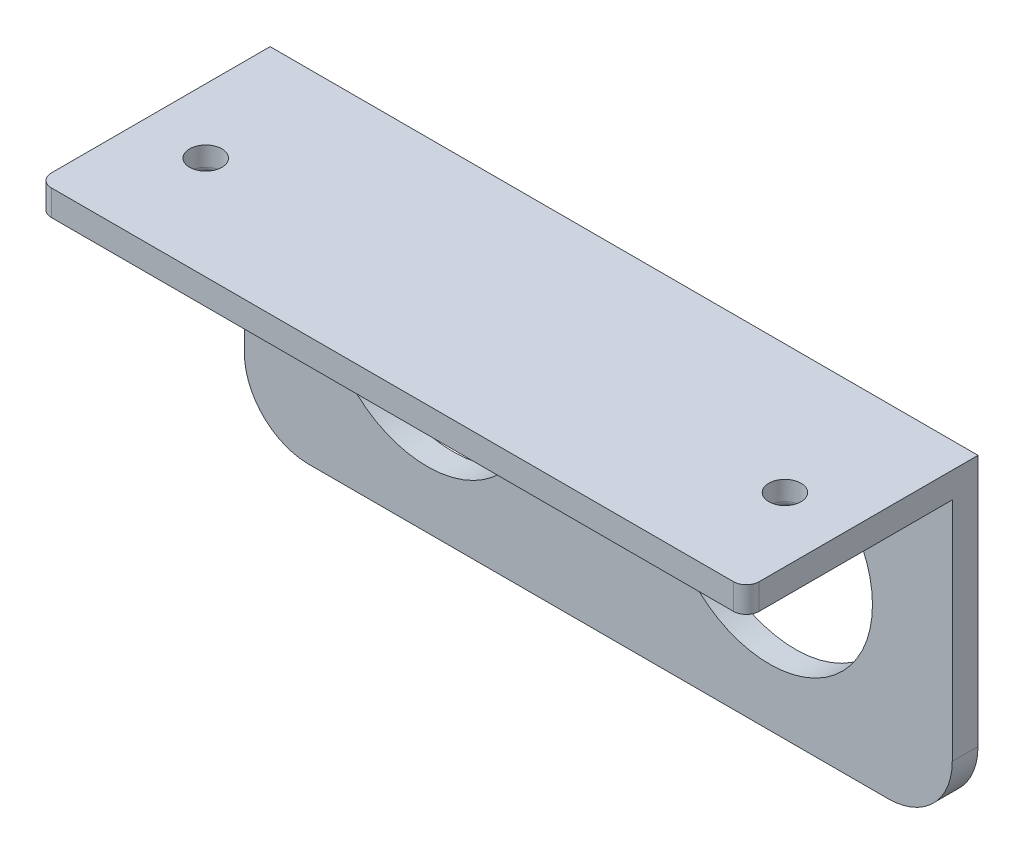
SolidWorks part; units mm, degrees
other "Markup1"
sketch "Sketch7" plane through (-20.0719, -0.3318, 12) normal (-0.8831, -0.2604, 0.3903) x (-0.3657, -0.1393, -0.9203)
other "Markup2"
sketch "Sketch23" plane through (-28.5719, 1.0682, 18) normal (-0.0368, -0.1105, 0.9932) x (-0.9991, 0.0251, -0.0342)
other "Markup3"
sketch "Sketch24" plane through (-28.5719, 1.0682, 18) normal (-0.0368, -0.1105, 0.9932) x (-0.9991, 0.0251, -0.0342)
ref_plane "Front Plane" through (0, 0, 0) normal (0, 0, 1) x (1, 0, 0)
ref_plane "Top Plane" through (0, 0, 0) normal (0, 1, 0) x (1, 0, 0)
ref_plane "Right Plane" through (0, 0, 0) normal (1, 0, 0) x (0, 0, -1)
sketch "Sketch1" plane through (0, 0, 0) normal (0, 0, 1) x (1, 0, 0)
  line L1 (-28.5719, 23.6682) -> (26.4281, 23.6682)
  line L2 (-28.5719, 23.6682) -> (-28.5719, 1.0682)
  line L3 (-28.5719, 1.0682) -> (26.4281, 1.0682)
  line L4 (26.4281, 23.6682) -> (26.4281, 1.0682)
  dimension "D1" = 55
  dimension "D2" = 22.6
extrude "Boss-Extrude1" add sketch "Sketch1" along normal blind 2 contours L1 L4 L3 L2
sketch "Sketch2" plane through (0, 0, 2) normal (0, 0, 1) x (1, 0, 0)
  line L1 (-28.5719, 23.6682) -> (26.4281, 23.6682) construction
  line L4 (-28.5719, 23.6682) -> (-28.5719, 1.0682) construction
  circle A0 centre (-14.3719, 13.5182) radius 8
  circle A1 centre (12.2281, 13.5182) radius 8
  dimension "D5" = 16
  dimension "D6" = 16
  dimension "D1" = 26.6
  dimension "D2" = 10.15
  dimension "D3" = 14.2
  dimension "D4" = 10.15
extrude "Cut-Extrude2" cut sketch "Sketch2" against normal blind 2 contours A0
extrude "Cut-Extrude3" cut sketch "Sketch2<4>" against normal blind 2
sketch "Sketch2<4>" plane through (0, 0, 2) normal (0, 0, 1) x (1, 0, 0) same geometry as "Sketch2"
sketch "Sketch5" plane through (0, 0, 2) normal (0, 0, 1) x (1, 0, 0)
  line L0 (-28.5719, 23.6682) -> (26.4281, 23.6682) construction
  line L1 (-6.5719, 23.6682) -> (4.4281, 23.6682)
  line L2 (-6.5719, 23.6682) -> (-6.5719, 18.1682)
  line L3 (-6.5719, 18.1682) -> (4.4281, 18.1682)
  line L4 (4.4281, 23.6682) -> (4.4281, 18.1682)
  line L5 (-28.5719, 23.6682) -> (-28.5719, 1.0682) construction
  dimension "D1" = 5.5
  dimension "D2" = 11
  dimension "D3" = 22
  dimension "D4" = 22
extrude "Cut-Extrude4" cut sketch "Sketch5" against normal blind 2 contours L3 L4 L1 L2
sketch "Sketch6" plane through (0, 0, 0) normal (0, 0, -1) x (-1, 0, 0)
  line L1 (28.5719, 25.6682) -> (-26.4281, 25.6682)
  line L2 (28.5719, 25.6682) -> (28.5719, 23.6682)
  line L3 (28.5719, 23.6682) -> (-26.4281, 23.6682)
  line L4 (-26.4281, 25.6682) -> (-26.4281, 23.6682)
  dimension "D1" = 55
  dimension "D2" = 2
extrude "Boss-Extrude2" add sketch "Sketch6" against normal blind 18 contours L1 L4 L3 L2
sketch "Sketch18" plane through (0, 23.6682, 0) normal (0, -1, 0) x (-1, 0, 0)
  line L0 (23.5719, -10) -> (-21.4281, -10)
  line L1 (-26.4281, -18) -> (-26.4281, -2) construction
  line L2 (28.5719, -18) -> (28.5719, -2) construction
  point P3 (1.0719, -10)
  dimension "D1" = 45
  dimension "D2" = 5
  dimension "D3" = 5
hole_wizard "M3x0.5 Tapped Hole1" positions "Sketch19" profile "Sketch20" tap size "M3x0.5" standard "ANSI Metric" end condition through all
sketch "Sketch19" plane through (0, 23.6682, 0) normal (0, -1, 0) x (-1, 0, 0)
  point P0 (-21.4281, -10)
sketch "Sketch20" plane through (21.4281, 23.6682, 10) normal (1, 0, 0) x (0, 0, -1)
  line L0 (0, 0) -> (0, 2)
  line L1 (0, 2) -> (1.25, 2)
  line L2 (1.25, 2) -> (1.25, 0)
  line L5 (1.25, 0) -> (0, 0)
  line L11 (0, -6.35) -> (0, 107.95) construction
  dimension "Thru Tap Drill Dia." = 2.5
  dimension "Thru Tap Drill Depth" = 2
cosmetic thread "Hole Thread1" parameters "D2"=3
hole_wizard "M3x0.5 Tapped Hole2" positions "Sketch21" profile "Sketch22" tap size "M3x0.5" standard "ANSI Metric" end condition through all
sketch "Sketch21" plane through (0, 23.6682, 0) normal (0, -1, 0) x (-1, 0, 0)
  point P0 (23.5719, -10)
sketch "Sketch22" plane through (-23.5719, 23.6682, 10) normal (1, 0, 0) x (0, 0, -1)
  line L0 (0, 0) -> (0, 2)
  line L1 (0, 2) -> (1.25, 2)
  line L2 (1.25, 2) -> (1.25, 0)
  line L5 (1.25, 0) -> (0, 0)
  line L11 (0, -6.35) -> (0, 107.95) construction
  dimension "Thru Tap Drill Dia." = 2.5
  dimension "Thru Tap Drill Depth" = 2
cosmetic thread "Hole Thread2" parameters "D2"=3
fillet "Fillet1" radius 5 1 edges at (-28.5719, 1.0682, 1) type face fillet first side face at (-1.0719, 1.0682, 1) second side face at (-28.5719, 16.8015, 6.6667)
fillet "Fillet2" radius 5 1 edges at (26.4281, 1.0682, 1) type face fillet first side face at (1.4281, 1.0682, 1) second side face at (26.4281, 16.8015, 6.6667)
fillet "Fillet4" radius 1.8 1 edges at (4.4281, 18.1682, 1)
fillet "Fillet5" radius 1.8 1 edges at (-6.5719, 18.1682, 1)
fillet "Fillet10" radius 1 2 edges at (26.4281, 24.6682, 18) (-28.5719, 24.6682, 18)
fillet "Fillet12" radius 0.5 1 edges at (-23.5719, 23.6682, 8.75)
fillet "Fillet13" radius 0.5 1 edges at (21.4281, 23.6682, 8.75)
sketch "Sketch25" plane through (0, 23.6682, 0) normal (0, -1, 0) x (1, 0, 0)
